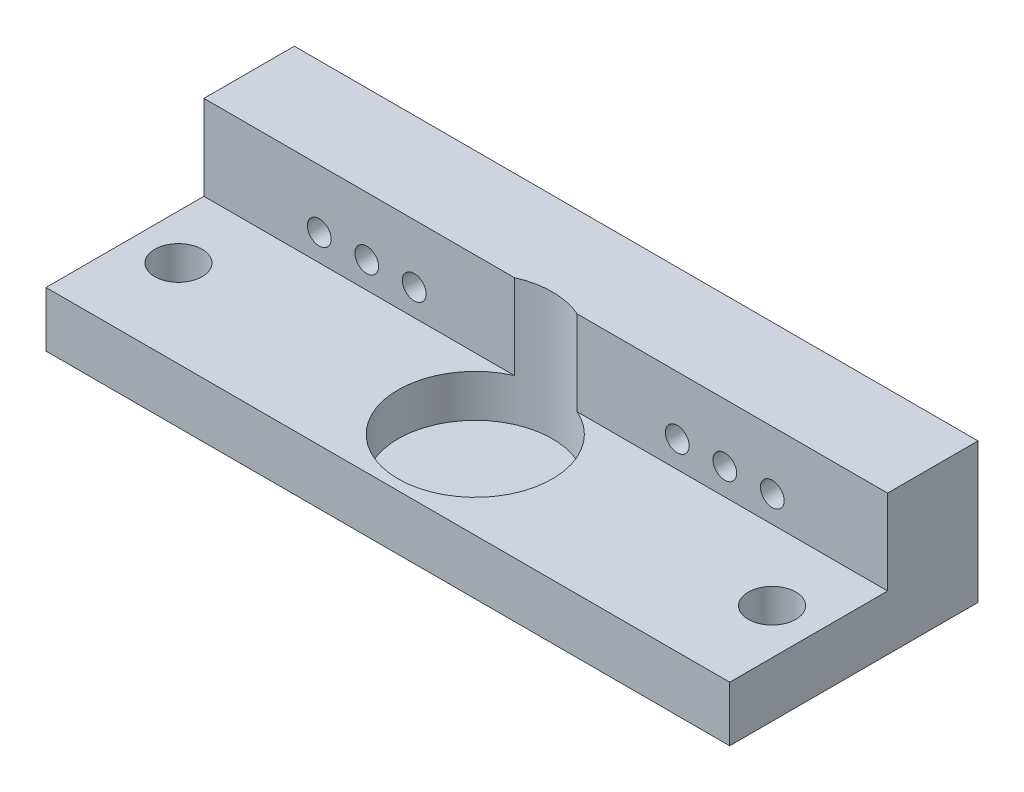
SolidWorks part; units mm, degrees
ref_plane "Front Plane" through (0, 0, 0) normal (0, 0, 1) x (1, 0, 0)
ref_plane "Top Plane" through (0, 0, 0) normal (0, 1, 0) x (1, 0, 0)
ref_plane "Right Plane" through (0, 0, 0) normal (1, 0, 0) x (0, 0, -1)
sketch "Sketch1" plane through (0, 0, 0) normal (0, 1, 0) x (1, 0, 0)
  line L1 (51.195, -13.095) -> (-51.195, -13.095)
  line L2 (51.195, -13.095) -> (51.195, 13.095)
  line L3 (51.195, 13.095) -> (-51.195, 13.095)
  line L4 (-51.195, -13.095) -> (-51.195, 13.095)
  line L5 (51.195, -13.095) -> (-51.195, 13.095) construction
  line L6 (51.195, 13.095) -> (-51.195, -13.095) construction
  point P0 (0, 0)
  dimension "D1" = 102.39
  dimension "D2" = 26.19
extrude "Boss-Extrude1" add sketch "Sketch1" along normal blind 1.905
sketch "Sketch2" plane through (0, 1.905, 0) normal (0, 1, 0) x (1, 0, 0)
  line L6 (51.195, -13.095) -> (-51.195, -13.095)
  line L7 (51.195, -13.095) -> (51.195, 13.095)
  line L8 (51.195, 13.095) -> (-51.195, 13.095)
  line L9 (-51.195, 13.095) -> (-51.195, -13.095)
  line L10 (-51.195, -13.095) -> (51.195, -13.095)
  line L11 (51.195, -13.095) -> (51.195, 13.095)
  line L12 (51.195, 13.095) -> (-51.195, 13.095)
  line L13 (-51.195, 13.095) -> (-51.195, -13.095)
  line L14 (-51.195, -13.095) -> (51.195, -13.095)
  line L15 (51.195, -13.095) -> (51.195, 13.095)
  line L16 (51.195, 13.095) -> (-51.195, 13.095)
  line L17 (-51.195, -13.095) -> (-51.195, 13.095)
  line L18 (51.195, -13.095) -> (-51.195, 13.095) construction
  line L19 (51.195, 13.095) -> (-51.195, -13.095) construction
  circle A0 centre (0, 0) radius 11.557
  circle A1 centre (-44.45, 0) radius 3.556
  circle A2 centre (44.45, 0) radius 3.556
  line M9 (-51.195, 13.095) -> (-51.195, -13.095)
  line M10 (-51.195, -13.095) -> (51.195, -13.095)
  line M11 (51.195, -13.095) -> (51.195, 13.095)
  line M12 (51.195, 13.095) -> (-51.195, 13.095)
  dimension "D1" = 23.114
  dimension "D2" = 7.112
  dimension "D3" = 7.112
  dimension "D4" = 44.45
  dimension "D5" = 44.45
  dimension "D19" = 0
extrude "Boss-Extrude3" add sketch "Sketch2" along normal blind 6.35 contours A2 A1 A0 M12 M9 M10 M11 region at (0, 1.905, 12.0381)
sketch "Sketch3" plane through (0, 8.255, 0) normal (0, 1, 0) x (1, 0, 0)
  line L0 (51.195, -13.095) -> (51.195, 13.095) construction
  line L1 (-51.195, 13.095) -> (51.195, 13.095)
  line L2 (-51.195, 13.095) -> (-51.195, 10.555)
  line L4 (51.195, 13.095) -> (51.195, 10.555)
  line L6 (-51.195, 10.555) -> (-4.707, 10.555)
  line L7 (4.707, 10.555) -> (51.195, 10.555)
  circle A2 centre (0, 0) radius 11.557 construction
  circle A3 centre (0, 0) radius 11.557 construction
  arc A4 (-4.707, 10.555) -> (4.707, 10.555) centre (0, 0) cw
  point P7 (-4.1421, 13.7392)
  dimension "D1" = 2.54
extrude "Boss-Extrude4" add sketch "Sketch3" along normal blind 12.7 contours L6 A4 L7 L4 L1 L2
sketch "Sketch4" plane through (0, 0, -13.095) normal (0, 0, -1) x (-1, 0, 0)
  line L2 (57.455, 14.211) -> (-57.545, 14.211) construction
  line L3 (57.455, 10.211) -> (-57.545, 10.211) construction
  line L4 (-51.195, 0) -> (51.195, 0)
  line L5 (51.195, 0) -> (51.195, 20.955)
  line L6 (51.195, 20.955) -> (-51.195, 20.955)
  line L7 (-51.195, 20.955) -> (-51.195, 0)
  line L8 (-51.195, 0) -> (51.195, 0)
  line L9 (51.195, 0) -> (51.195, 20.955)
  line L10 (51.195, 20.955) -> (-51.195, 20.955)
  line L11 (-51.195, 20.955) -> (-51.195, 0)
  line L12 (-57.545, 14.211) -> (-57.545, 10.211) construction
  line L13 (-57.545, 10.211) -> (-57.7964, 10.4194)
  line L14 (-57.545, 12.211) -> (57.455, 12.211) construction
  circle A0 centre (-33.923, 12.211) radius 1.778
  circle A1 centre (-26.811, 12.211) radius 1.778
  circle A2 centre (-19.699, 12.211) radius 1.778
  circle A3 centre (19.699, 12.211) radius 1.778
  circle A4 centre (26.811, 12.211) radius 1.778
  circle A5 centre (33.923, 12.211) radius 1.778
  dimension "D7" = 3.556
  dimension "D2" = 7.112
  dimension "D3" = 7.112
  dimension "D4" = 39.398
  dimension "D5" = 7.112
  dimension "D6" = 7.112
  dimension "D8" = 17.272
  dimension "D1" = 0
extrude "Cut-Extrude1" cut sketch "Sketch4" against normal up to next contours A5 | A4 | A3 | A0 | A1 | A2 | A4 region at (-19.699, 12.211, -13.095) region at (-26.811, 12.211, -13.095) region at (-33.923, 12.211, -13.095)
sketch "Sketch5" plane through (0, 0, -13.095) normal (0, 0, -1) x (-1, 0, 0)
  line L1 (-51.195, 20.955) -> (51.195, 20.955)
  line L2 (-51.195, 20.955) -> (-51.195, 0)
  line L3 (-51.195, 0) -> (51.195, 0)
  line L4 (51.195, 20.955) -> (51.195, 0)
  circle A0 centre (-33.923, 12.211) radius 1.778 construction
  circle A1 centre (-26.811, 12.211) radius 1.778 construction
  circle A2 centre (-19.699, 12.211) radius 1.778 construction
  circle A3 centre (19.699, 12.211) radius 1.778 construction
  circle A4 centre (26.811, 12.211) radius 1.778 construction
  circle A5 centre (33.923, 12.211) radius 1.778 construction
  circle A6 centre (33.923, 12.211) radius 1.778
  circle A7 centre (26.811, 12.211) radius 1.778
  circle A8 centre (19.699, 12.211) radius 1.778
  circle A9 centre (-19.699, 12.211) radius 1.778
  circle A10 centre (-26.811, 12.211) radius 1.778
  circle A11 centre (-33.923, 12.211) radius 1.778
extrude "Boss-Extrude5" add sketch "Sketch5" along normal blind 11
